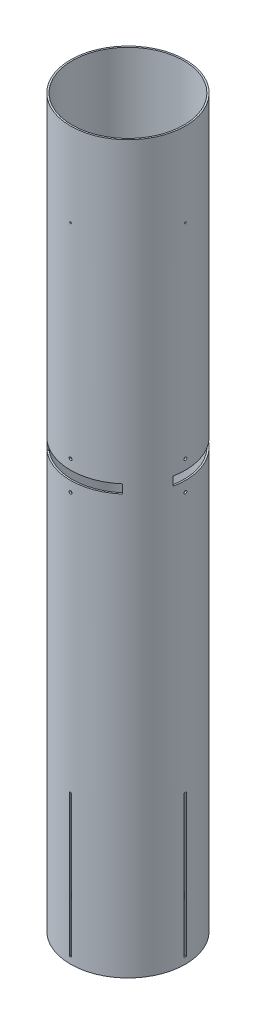
SolidWorks part; units mm, degrees
material "A-Glass Fiber"
ref_plane "Front Plane" through (0, 0, 0) normal (0, 0, 1) x (1, 0, 0)
ref_plane "Top Plane" through (0, 0, 0) normal (0, 1, 0) x (1, 0, 0)
ref_plane "Right Plane" through (0, 0, 0) normal (1, 0, 0) x (0, 0, -1)
sketch "Sketch1" plane through (0, 0, 0) normal (0, 1, 0) x (1, 0, 0)
  circle A0 centre (0, 0) radius 76.2
  circle A1 centre (0, 0) radius 78.359
  dimension "D1" = 152.4
  dimension "D2" = 156.718
extrude "Boss-Extrude1" add sketch "Sketch1" along normal blind 990.6
ref_plane "Plane1" through (0, 0, 0) normal (0.7071, 0, 0.7071) x (0.7071, 0, -0.7071)
ref_axis "Axis1" through (0, 990.6, 0) along (0, -1, 0)
sketch "Sketch2" plane through (0, 0, 0) normal (1, 0, 0) x (0, 0, -1)
  line L0 (0, 0) -> (0, 8.89)
  line L1 (1.5875, 8.89) -> (-1.5875, 8.89)
  line L2 (1.5875, 8.89) -> (1.5875, 203.2)
  line L3 (1.5875, 203.2) -> (-1.5875, 203.2)
  line L4 (-1.5875, 8.89) -> (-1.5875, 203.2)
  line L5 (1.5875, 8.89) -> (-1.5875, 203.2) construction
  line L6 (1.5875, 203.2) -> (-1.5875, 8.89) construction
  line L7 (78.359, 990.6) -> (-78.359, 990.6) construction
  line L8 (78.359, 990.6) -> (-78.359, 990.6)
  line L9 (0, 990.6) -> (0, 597.4705)
  line L10 (-78.359, 0) -> (78.359, 0) construction
  circle A0 centre (0, 597.4705) radius 2
  circle A1 centre (0, 876.3) radius 1.0922
  point P0 (0, 106.045)
  dimension "D4" = 4
  dimension "D6" = 2.1844
  dimension "D1" = 3.175
  dimension "D2" = 194.31
  dimension "D5" = 597.4705
  dimension "D3" = 203.2
  dimension "D7" = 114.3
extrude "Fin Slots" cut sketch "Sketch2" against normal through all contours L4 L1 L2 L3 region at (0, 106.045, 0)
pattern_circular "CirPattern1" count 4 over 360 about axis through (0, 0, 0) along (0, 1, 0) of "Fin Slots" reverse direction yes
extrude "Cut-Extrude2" cut sketch "Sketch2<3>" against normal through all contours A0 region at (0, 598.8447, -1.3742)
sketch "Sketch2<3>" plane through (0, 0, 0) normal (1, 0, 0) x (0, 0, -1) same geometry as "Sketch2"
pattern_circular "CirPattern2" count 4 over 360 about axis through (0, 990.6, 0) along (0, -1, 0) of "Cut-Extrude2"
sketch "Sketch3" plane through (0, 0, 0) normal (0.7071, 0, 0.7071) x (0.7071, 0, -0.7071)
  line L0 (0, 0) -> (0, 127) construction
  circle A0 centre (0, 127) radius 3.175
  dimension "D1" = 6.35
  dimension "D2" = 127
extrude "Cut-Extrude3" cut sketch "Sketch3" against normal through all
ref_plane "Plane3" through (0, 583.8825, 0) normal (0, 1, 0) x (1, 0, 0)
sketch "Sketch7" plane through (0, 583.8825, 0) normal (0, 1, 0) x (1, 0, 0)
  line L0 (0, 0) -> (-76.8534, -15.2871)
  line L1 (0, 0) -> (0, 93.232) construction
  line L2 (0, 0) -> (-25.1877, 74.2005)
  line L3 (-78.359, 0) -> (0, 0) construction
  arc A0 (-78.3335, 2) -> (-78.3335, -2) centre (0, 0) ccw construction
  circle A1 centre (0, 0) radius 76.2 construction
  circle A2 centre (0, 0) radius 78.359
  circle A3 centre (0, 0) radius 78.359
  circle A4 centre (0, 0) radius 76.2
  circle A5 centre (0, 0) radius 78.359 construction
  arc A6 (2, 78.3335) -> (-2, 78.3335) centre (0, 0) ccw construction
  arc A7 (-78.3335, 2) -> (-78.3335, -2) centre (0, 0) ccw
  arc A8 (2, 78.3335) -> (-2, 78.3335) centre (0, 0) ccw
  dimension "D1" = 82.5
  dimension "D3" = 11.25
  dimension "D2" = 0
extrude "Cut-Extrude4" cut sketch "Sketch7" against normal blind 12.065 contours A4 A3 L0 region at (-75.9984, 583.8825, 14.0521)
pattern_circular "CirPattern3" count 3 over 360 about axis through (0, 990.6, 0) along (0, -1, 0) of "Cut-Extrude4"
extrude "Shear Screw Holes" cut sketch "Sketch2<4>" against normal through all contours L9 A1 | L9 A1 region at (0, 876.3, -0.4635) region at (0, 876.3, 0.4635)
sketch "Sketch2<4>" plane through (0, 0, 0) normal (1, 0, 0) x (0, 0, -1) same geometry as "Sketch2"
pattern_circular "Shear Screw Pattern" count 4 over 360 about axis through (0, 990.6, 0) along (0, -1, 0) of "Shear Screw Holes"
pattern_linear "LPattern1" count 2 spacing 39.6916 along (0, -1, 0) of "Cut-Extrude2", "CirPattern2"
equation "\"D1@Boss-Extrude1\" = \"Aft_Section_Length\""
equation "\"AB_Coupler_OD_Length\"= 1in"
equation "\"AB_Coupling_Section_Length\"= 0.375in"
equation "\"AB_Coupler_Length\"= \"AB_Coupler_OD_Length\" + \"AB_Coupling_Section_Length\" * 2"
equation "\"AB_Coupler_Num_Screws\"= 4"
equation "\"AB_Coupling_Screw_Diameter\"= 0.15748in"
equation "\"Aft_Section_Length\"= 39in"
equation "\"D4@Sketch2\"=\"AB_Coupling_Screw_Diameter\""
equation "\"D1@CirPattern2\"=\"AB_Coupler_Num_Screws\""
equation "\"Rail_Nut_From_Bottom\"= 5in"
equation "\"Rail_Nut_Diam\"= 0.25in"
equation "\"D1@Sketch3\"=\"Rail_Nut_Diam\""
equation "\"D2@Sketch3\"=\"Rail_Nut_From_Bottom\""
equation "\"AB_BKHD_Thickness\"= 0.375in"
equation "\"AB_Mount_From_Bottom\"= 23.175in"
equation "\"Cutout_Angle\"= 80"
equation "\"Shear_Screw_Diameter\"= 0.086in"
equation "\"D6@Sketch2\"=\"Shear_Screw_Diameter\""
equation "\"Shear_Screw_Coupler_Location\"= 4.5in"
equation "\"D7@Sketch2\"=\"Shear_Screw_Coupler_Location\""
equation "\"Bodytube_OD\"= 6.17in"
equation "\"Bodytube_ID\"= 5.998in"
equation "\"Motor_OD\"= 4in"
equation "\"Fwd_Tube_Length\"= 40in"
equation "\"Mid_Tube_Length\"= 1in"
equation "\"Mid_Coupler_Length\"= 13in"
equation "\"AB_Paddle_Height\"= 0.375in"
equation "\"Num_Cutouts\"= 3"
equation "\"AB_Coupler_OD\"= 6.17in"
equation "\"AB_Coupler_ID\"= 5.75in"
equation "\"AB_Coupler_Surface_Diameter\"= 5.998in"
equation "\"AB_Central_Bushing_Length\"= .4724in"
equation "\"Lead_Screw_Dist\"= 3.4in"
equation "\"Lead_Screw_Diam\"= 0.386in"
equation "\"Lead_Screw_Length\"= (\"Mid_Coupler_Length\" + 2*0.375in + 2*0.5in)"
equation "\"Paddle_Pin_Offset\"= .25in"
equation "\"Paddle_Pin_Radius\"= 2.25in"
equation "\"SS_Paddle_Pin_Radius\"= 2.25*0.66in"
equation "\"Paddle_Gear_OD\"= 3.2in"
equation "\"Drive_Gear_OD\"= 1.7in"
equation "\"Fwd_BKHD_From_Top\"= 18in"
equation "\"Fin_Thickness\"= .118in"
equation "\"Guiderail_Cutout_Diameter\"= 1.5in"
equation "\"DB9_Hole_Dist\"= 25mm"
equation "\"DB9_Relief_Width\"= 0.47in"
equation "\"DB9_Relief_Hole_Offset\"= 0.09in"
equation "\"Airbrakes_Wire_Hole_Dia\"= .25in"
equation "\"Airbrakes_Wire_Hole_Dist\"= 1.1in"
equation "\"Servo_Gear_Offset\"= 0.5in"
